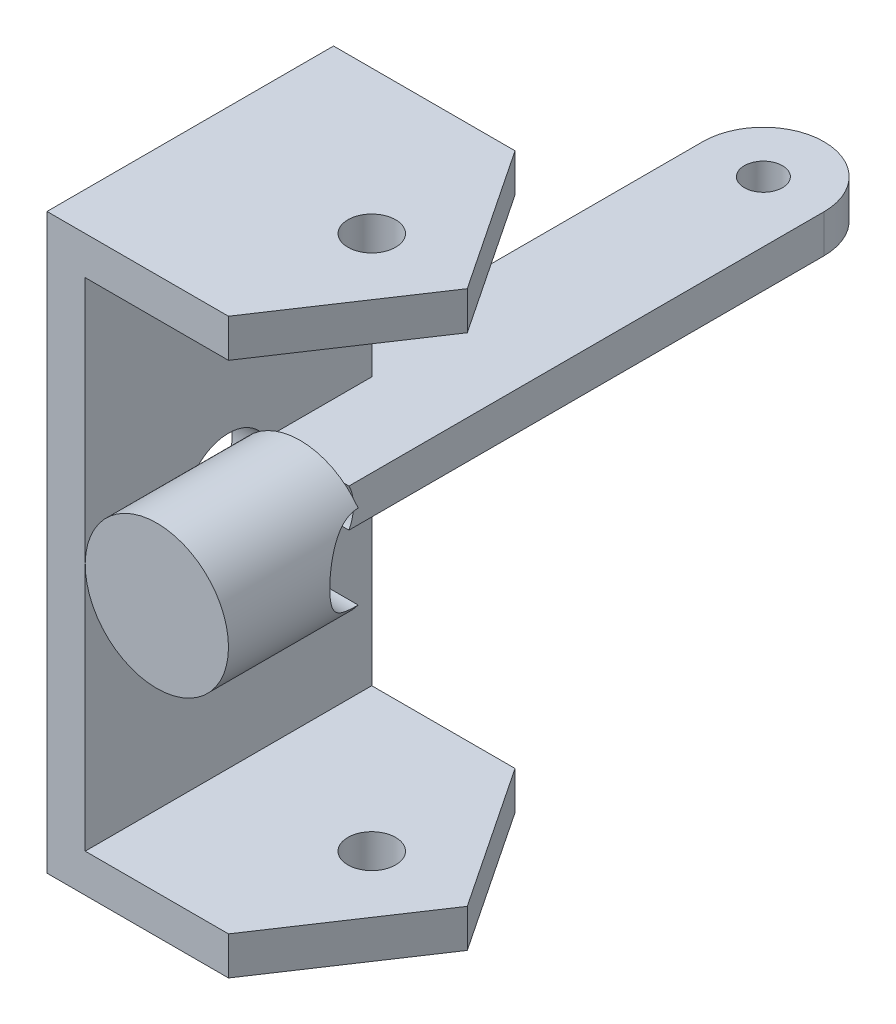
SolidWorks part; units mm, degrees
ref_plane "Front Plane" through (0, 0, 0) normal (0, 0, 1) x (1, 0, 0)
ref_plane "Top Plane" through (0, 0, 0) normal (0, 1, 0) x (1, 0, 0)
ref_plane "Right Plane" through (0, 0, 0) normal (1, 0, 0) x (0, 0, -1)
sketch "Sketch2" plane through (0, 0, 0) normal (1, 0, 0) x (0, 0, -1)
  line L1 (30, -60) -> (-30, -60)
  line L2 (30, -60) -> (30, 60)
  line L3 (30, 60) -> (-30, 60)
  line L4 (-30, -60) -> (-30, 60)
  line L5 (30, -60) -> (-30, 60) construction
  line L6 (30, 60) -> (-30, -60) construction
  point P0 (0, 0)
  dimension "D1" = 120
  dimension "D2" = 60
extrude "Boss-Extrude1" add sketch "Sketch2" along normal blind 8
sketch "Sketch3" plane through (8, 0, 0) normal (1, 0, 0) x (0, 0, -1)
  line L0 (30, -60) -> (30, 60) construction
  line L1 (-30, 60) -> (30, 60)
  line L2 (-30, 60) -> (-30, 52)
  line L3 (-30, 52) -> (30, 52)
  line L4 (30, 60) -> (30, 52)
  dimension "D1" = 8
extrude "Boss-Extrude2" add sketch "Sketch3" along normal blind 50
sketch "Sketch4" plane through (0, 60, 0) normal (0, 1, 0) x (1, 0, 0)
  line L0 (58, 0) -> (38, -30)
  line L1 (58, 30) -> (58, -30) construction
  line L2 (58, -30) -> (0, -30) construction
  line L3 (58, 0) -> (38, 30)
  line L4 (58, 30) -> (0, 30) construction
  line L5 (38, -30) -> (58, -30)
  line L6 (58, -30) -> (58, 30)
  line L7 (58, 30) -> (38, 30)
  line M4 (0, -30) -> (58, -30)
  line M5 (58, -30) -> (58, 30)
  line M6 (58, 30) -> (0, 30)
  dimension "D1" = 20
  dimension "D2" = 20
extrude "Cut-Extrude1" cut sketch "Sketch4" against normal blind 50 contours L3 M5 M6 | L0 M5 M4 region at (51.3333, 60, 20) region at (51.3333, 60, -20)
sketch "Sketch5" plane through (0, 60, 0) normal (0, 1, 0) x (1, 0, 0)
  line L0 (38, 30) -> (38, -30) construction
  circle A0 centre (38, 0) radius 5
  dimension "D1" = 10
extrude "Cut-Extrude2" cut sketch "Sketch5" against normal through all
mirror "Mirror1" about plane through (0, 0, 0) normal (0, 1, 0) of "Boss-Extrude2", "Cut-Extrude1", "Cut-Extrude2"
sketch "Sketch7" plane through (0, 0, 0) normal (0, 1, 0) x (1, 0, 0)
  line L1 (0, 0) -> (25.4, 0)
  line L2 (0, 0) -> (0, 120)
  line L3 (0, 120) -> (25.4, 120)
  line L4 (25.4, 0) -> (25.4, 120)
  dimension "D1" = 120
  dimension "D2" = 25.4
extrude "Boss-Extrude3" add sketch "Sketch7" along normal mid plane 8
fillet "Fillet1" radius 12.7 2 edges at (0, 0, -120) (25.4, 0, -120)
sketch "Sketch9" plane through (0, 4, 0) normal (0, 1, 0) x (1, 0, 0)
  circle A0 centre (12.7, 107.3) radius 4
  arc A1 (25.4, 107.3) -> (12.7, 120) centre (12.7, 107.3) ccw construction
  dimension "D1" = 8
extrude "Cut-Extrude4" cut sketch "Sketch9" against normal through all
sketch "Sketch11" plane through (0, 0, 0) normal (0, 0, 1) x (1, 0, 0)
  line L0 (8, 52) -> (8, -52) construction
  circle A0 centre (23, 0) radius 15
  point P4 (0, 0)
  dimension "D1" = 30
extrude "Boss-Extrude4" add sketch "Sketch11" along normal blind 30 separate body
sketch "Sketch6" plane through (8, 0, 0) normal (1, 0, 0) x (0, 0, -1)
  circle A0 centre (0, 0) radius 8.7905
extrude "Cut-Extrude3" cut sketch "Sketch6" along normal through all both and the other way through all
